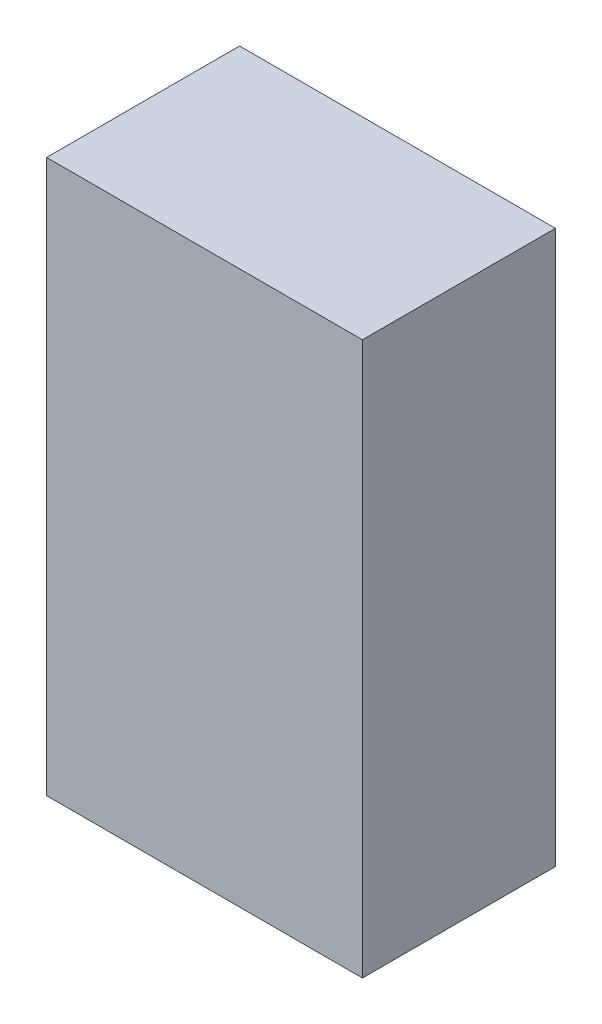
SolidWorks part; units mm, degrees
ref_plane "Front Plane" through (0, 0, 0) normal (0, 0, 1) x (1, 0, 0)
ref_plane "Top Plane" through (0, 0, 0) normal (0, 1, 0) x (1, 0, 0)
ref_plane "Right Plane" through (0, 0, 0) normal (1, 0, 0) x (0, 0, -1)
sketch "Sketch1" plane through (0, 0, 0) normal (0, 0, 1) x (1, 0, 0)
  line L1 (0, 0) -> (36, 0)
  line L2 (0, 0) -> (0, -63)
  line L3 (0, -63) -> (36, -63)
  line L4 (36, 0) -> (36, -63)
  line L5 (2, -2) -> (34, -2)
  line L6 (2, -2) -> (2, -61)
  line L7 (2, -61) -> (34, -61)
  line L8 (34, -2) -> (34, -61)
  point P8 (-5.1787, 3.8385)
  point P9 (-1.6252, -58.3476)
  point P10 (31.7381, -59.0386)
  point P15 (36.3645, 1)
  dimension "D1" = 2
  dimension "D2" = 2
  dimension "D3" = 2
  dimension "D4" = 2
  dimension "D5" = 32
  dimension "D6" = 59
extrude "Wall_Height" add sketch "Sketch1" along normal blind 20
extrude "Roof" add sketch "Sketch1<3>" along normal blind 2 from surface contours L8 L5 L6 L7 | L4 L1 L2 L3 L5 L8 L7 L6 region at (18, -0.7256, 0) region at (18, -31.5, 0) starting at face at (18, -31.5, 20)
sketch "Sketch1<3>" plane through (0, 0, 0) normal (0, 0, 1) x (1, 0, 0) same geometry as "Sketch1"
